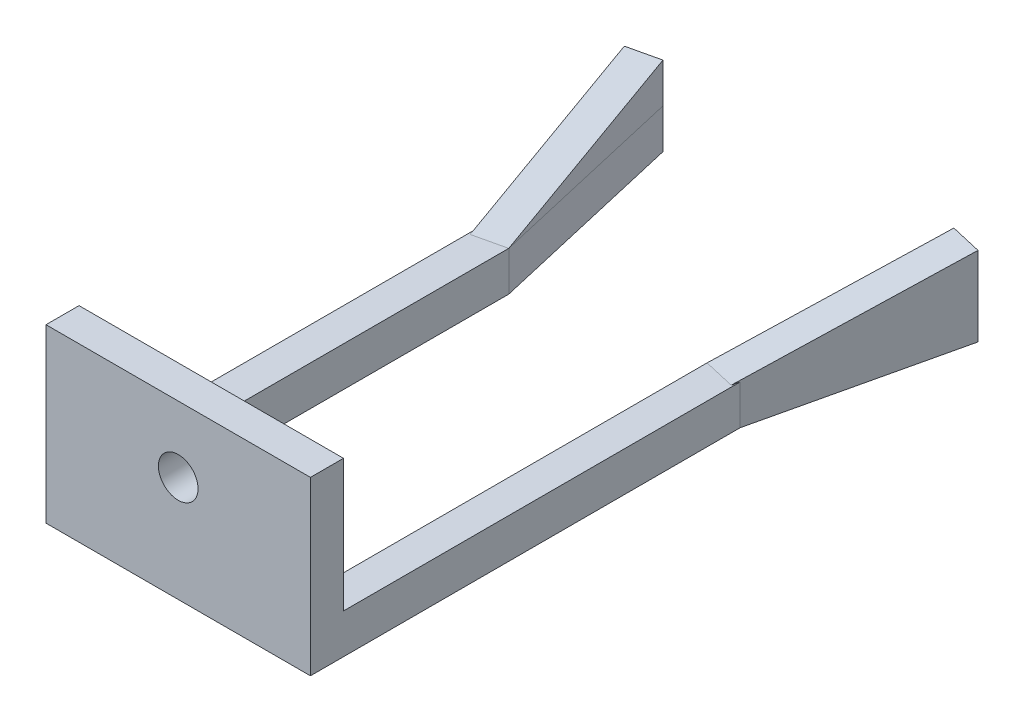
SolidWorks part; units mm, degrees
ref_plane "Front Plane" through (0, 0, 0) normal (0, 0, 1) x (1, 0, 0)
ref_plane "Top Plane" through (0, 0, 0) normal (0, 1, 0) x (1, 0, 0)
ref_plane "Right Plane" through (0, 0, 0) normal (1, 0, 0) x (0, 0, -1)
sketch "Sketch1" plane through (0, 0, 0) normal (0, 1, 0) x (1, 0, 0)
  line L0 (0, -55) -> (0, 55) construction
  line L6 (-10, -2.5) -> (10, -2.5)
  line L12 (7.5, 0) -> (7.5, 30)
  line L15 (-7.5, 0) -> (-7.5, 30)
  line L16 (-7.5, 0) -> (7.5, 0)
  line L17 (-10, 30) -> (-10, -2.5)
  line L18 (10, -2.5) -> (10, 30)
  line L19 (-7.5, 30) -> (-11.0008, 45.1635)
  line L20 (-11.0008, 45.1635) -> (-13.3743, 44.6156)
  line L21 (-13.3743, 44.6156) -> (-10, 30)
  line L22 (11.0008, 45.1635) -> (13.3743, 44.6156)
  line L23 (13.3743, 44.6156) -> (10, 30)
  line L24 (7.5, 30) -> (11.0008, 45.1635)
  point P0 (0, 0)
  point P7 (0, 0)
  point P15 (0, 0)
  point P16 (0, 0)
  point P19 (0, 0)
  point P20 (0, 0)
  point P21 (0, 0)
  point P22 (0, 0)
  point P23 (0, 0)
  point P24 (0, 0)
  dimension "D1" = 15
  dimension "D2" = 2.5
  dimension "D3" = 2.5
  dimension "D4" = 15
  dimension "D5" = 167
  dimension "D6" = 30
extrude "Boss-Extrude1" add sketch "Sketch1" along normal blind 3
sketch "Sketch2" plane through (-0.5449, 0, 0.1258) normal (0.9744, 0, -0.225) x (-0.225, 0, -0.9744)
  line L0 (30.9182, 3) -> (46.4806, 6)
  line L1 (46.4806, 6) -> (46.4806, 3)
  line L2 (30.9182, 3) -> (46.4806, 3) construction
  line L3 (30.9182, 3) -> (46.4806, 3)
  point P5 (46.4806, 5.5172)
  dimension "D1" = 3
extrude "Boss-Extrude2" add sketch "Sketch2" against normal up to surface (2.4359 mm away) separate body up to face at (-11.6871, 1.5, -37.3078)
mirror "Mirror4" about plane through (0, 0, 0) normal (1, 0, 0) of "Boss-Extrude2"
fillet "Fillet1" [suppressed] radius 2
sketch "Sketch3" plane through (0, 3, 0) normal (0, 1, 0) x (1, 0, 0)
  line L0 (10, -2.5) -> (10, 30) construction
  line L1 (-10, -2.5) -> (10, -2.5)
  line L2 (-10, -2.5) -> (-10, 0)
  line L3 (-10, 0) -> (10, 0)
  line L4 (10, -2.5) -> (10, 0)
  line L5 (7.5, 0) -> (-7.5, 0) construction
extrude "Boss-Extrude3" add sketch "Sketch3" along normal blind 10
sketch "Sketch4" plane through (0, 0, 0) normal (0, 0, -1) x (-1, 0, 0)
  line L0 (10, 13) -> (10, 3) construction
  circle A0 centre (0, 8) radius 1.5
  point P4 (10, 8)
  point P5 (-3.6035, 8)
  dimension "D1" = 3
extrude "Cut-Extrude1" cut sketch "Sketch4" against normal through all
